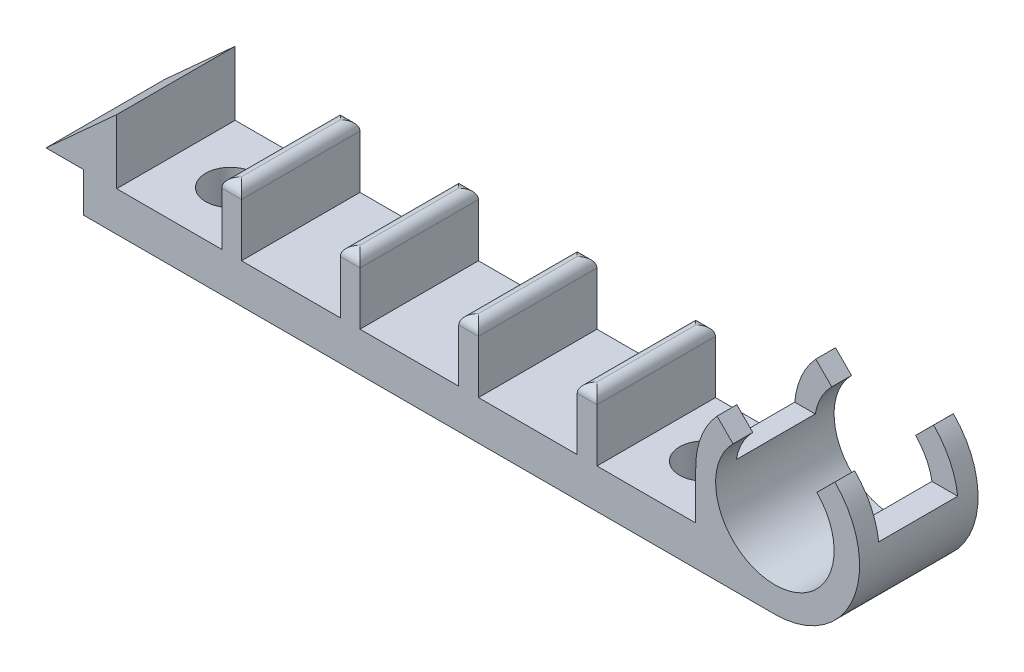
SolidWorks part; units mm, degrees
ref_plane "Plan de face" through (0, 0, 0) normal (0, 0, 1) x (1, 0, 0)
ref_plane "Plan de dessus" through (0, 0, 0) normal (0, 1, 0) x (1, 0, 0)
ref_plane "Plan de droite" through (0, 0, 0) normal (1, 0, 0) x (0, 0, -1)
sketch "Esquisse1" plane through (0, 0, 0) normal (0, 0, 1) x (1, 0, 0)
  line L0 (-48.3206, 10.5264) -> (-55.4805, 4.0264)
  line L1 (-55.4805, 4.0264) -> (-51.6608, 4.0264)
  line L2 (-51.6608, 0.0264) -> (18.3392, 0.0264)
  line L3 (10.3227, 8.6081) -> (10.3227, 4.0264)
  line L4 (10.3227, 4.0264) -> (0.3227, 4.0264)
  line L5 (0.3227, 4.0264) -> (0.3227, 10.3985)
  line L6 (0.3227, 10.3985) -> (-1.6773, 10.3985)
  line L7 (-1.6773, 10.3985) -> (-1.6773, 4.0264)
  line L8 (-1.6773, 4.0264) -> (-11.6773, 4.0264)
  line L9 (-11.6773, 4.0264) -> (-11.6773, 10.3985)
  line L10 (-11.6773, 10.3985) -> (-13.6773, 10.3985)
  line L11 (-13.6773, 10.3985) -> (-13.6773, 4.0264)
  line L12 (-13.6773, 4.0264) -> (-23.6773, 4.0264)
  line L13 (-23.6773, 4.0264) -> (-23.6773, 10.3985)
  line L14 (-23.6773, 10.3985) -> (-25.6773, 10.3985)
  line L15 (-25.6773, 10.3985) -> (-25.6773, 4.0264)
  line L16 (-25.6773, 4.0264) -> (-35.6773, 4.0264)
  line L17 (-35.6773, 4.0264) -> (-35.6773, 10.3985)
  line L18 (-35.6773, 10.3985) -> (-37.6773, 10.3985)
  line L19 (-37.6773, 10.3985) -> (-37.6773, 4.0264)
  line L20 (-37.6773, 4.0264) -> (-44.9805, 4.0264)
  line L21 (-44.9805, 4.0264) -> (-48.3206, 4.0264)
  line L22 (-48.3206, 4.0264) -> (-48.3206, 10.5264)
  line L23 (-51.6608, 4.0264) -> (-51.6608, 0.0264)
  line L24 (-51.6608, 0.0264) -> (-51.7327, -0.0814)
  arc A0 (18.3392, 0.0264) -> (18.3392, 17.1898) centre (18.3392, 8.6081) ccw
  arc A1 (18.3392, 17.1898) -> (10.3227, 8.6081) centre (18.6218, 8.8908) ccw
  dimension "D1" = 70
  dimension "D2" = 4
  dimension "D3" = 4
  dimension "D4" = 2
  dimension "D5" = 2
  dimension "D6" = 2
  dimension "D7" = 2
  dimension "D8" = 10
  dimension "D9" = 10
  dimension "D10" = 10
  dimension "D11" = 10
  dimension "D12" = 6.5
extrude "Boss.-Extru.1" add sketch "Esquisse1" along normal blind 12 contours L2 A0 A1 L3 L4 L5 L6 L7 L8 L9 L10 L11 L12 L13 L14 L15 L16 L17 L18 L19 L20 L21 L22 L0 L1 L23
sketch "Esquisse2" plane through (0, 0, 12) normal (0, 0, 1) x (1, 0, 0)
  circle A0 centre (18.3392, 8.6081) radius 6
  arc A1 (18.3392, 0.0264) -> (18.3392, 17.1898) centre (18.3392, 8.6081) ccw construction
  dimension "D1" = 0
  dimension "D2" = 12
extrude "Enlèv. mat.-Extru.1" cut sketch "Esquisse2" against normal up to surface (12 mm away) up to face at (-19.6061, 6.7817, 0)
ref_plane "Plan1" through (0, 0, 2) normal (0, 0, 1) x (1, 0, 0)
sketch "Esquisse5" plane through (0, 0, 2) normal (0, 0, 1) x (1, 0, 0)
  line L1 (7.1013, 19.398) -> (29.2922, 19.398)
  line L2 (7.1013, 19.398) -> (7.1013, 9.6416)
  line L3 (7.1013, 9.6416) -> (29.2922, 9.6416)
  line L4 (29.2922, 19.398) -> (29.2922, 9.6416)
extrude "Enlèv. mat.-Extru.2" cut sketch "Esquisse5" along normal blind 8 contours L1 L4 L3 L2
sketch "Esquisse6" plane through (0, 0, 0) normal (0, 0, 1) x (1, 0, 0)
  line L0 (6.0905, 20.9043) -> (18.3392, 8.6081)
  line L1 (18.3392, 8.6081) -> (30.683, 20.9043)
  line L2 (30.683, 20.9043) -> (6.0905, 20.9043)
  line L3 (6.0905, 20.9043) -> (9.3766, 14.8539)
  circle A0 centre (18.3392, 8.6081) radius 6 construction
  dimension "D1" = 90
  dimension "D2" = 0
extrude "Enlèv. mat.-Extru.3" cut sketch "Esquisse6" along normal through all contours L0 L1 L2
fillet "Congé1" radius 1 16 edges at (-35.6773, 10.3985, 6) (-36.6773, 10.3985, 12) (-37.6773, 10.3985, 6) (-36.6773, 10.3985, 0) (-11.6773, 10.3985, 6) (-12.6773, 10.3985, 12) (-13.6773, 10.3985, 6) (-12.6773, 10.3985, 0) (-23.6773, 10.3985, 6) (-24.6773, 10.3985, 12) (-25.6773, 10.3985, 6) (-24.6773, 10.3985, 0) (0.3227, 10.3985, 6) (-0.6773, 10.3985, 12) (-1.6773, 10.3985, 6) (-0.6773, 10.3985, 0)
sketch "Esquisse7" plane through (0, 4.0264, 0) normal (0, 1, 0) x (1, 0, 0)
  line L0 (-37.6773, -12) -> (-37.6773, 0) construction
  line L1 (0.3227, -12) -> (0.3227, 0) construction
  circle A0 centre (-42.6773, -6.1322) radius 2.5
  circle A1 centre (5.3227, -6.1322) radius 2.5
  point P4 (-37.6773, -6)
  dimension "D3" = 5
  dimension "D4" = 5
  dimension "D1" = 5
  dimension "D2" = 5
extrude "Enlèv. mat.-Extru.4" cut sketch "Esquisse7" against normal up to surface (4 mm away) up to face at (-16.6608, 0.0264, 6)
